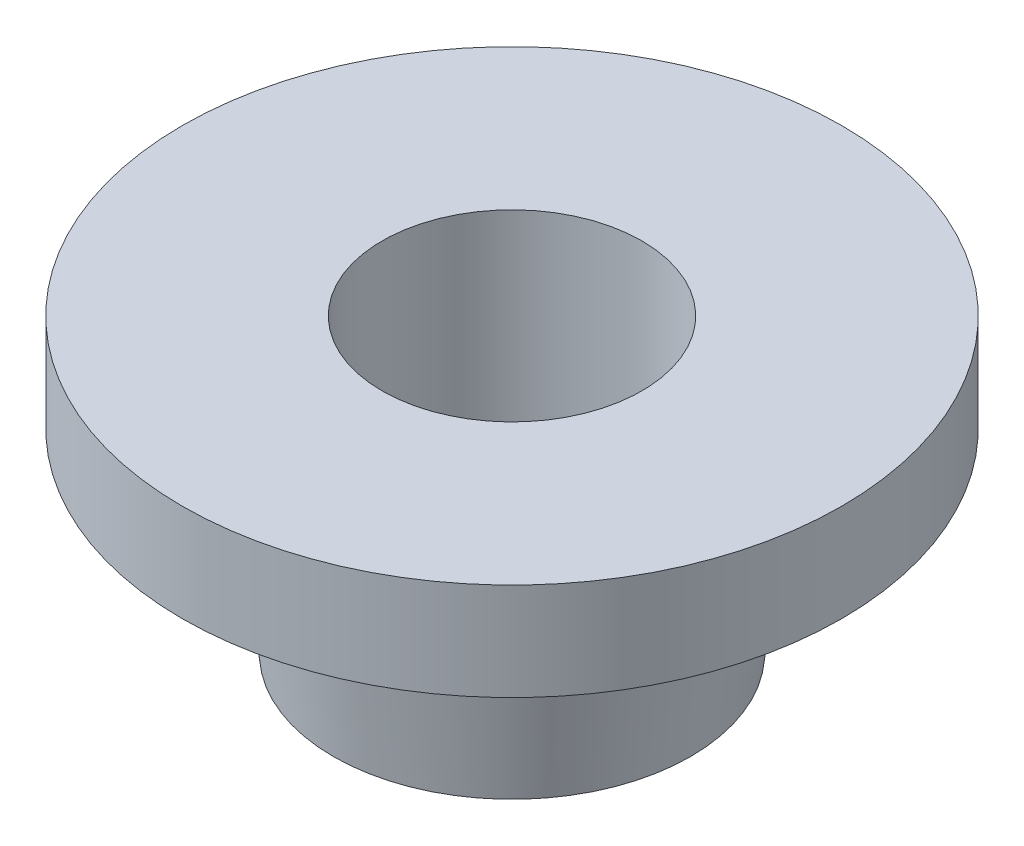
SolidWorks part; units mm, degrees
ref_plane "Front Plane" through (0, 0, 0) normal (0, 0, 1) x (1, 0, 0)
ref_plane "Top Plane" through (0, 0, 0) normal (0, 1, 0) x (1, 0, 0)
ref_plane "Right Plane" through (0, 0, 0) normal (1, 0, 0) x (0, 0, -1)
sketch "Sketch1" plane through (0, 0, 0) normal (0, 0, 1) x (1, 0, 0)
  line L1 (-4, 9) -> (-10.15, 9)
  line L2 (-10.15, 9) -> (-10.15, 6)
  line L3 (-10.15, 6) -> (-6.15, 6)
  line L4 (-6.15, 6) -> (-5.5, 0)
  line L5 (-5.5, 0) -> (-4, 0)
  line L6 (0, 0) -> (0, 9) construction
  line L8 (-4, 9) -> (-4, 0)
  dimension "D1" = 8
  dimension "D2" = 11
  dimension "D3" = 12.3
  dimension "D4" = 6
  dimension "D5" = 3
  dimension "D6" = 4
revolve "Revolve1" add sketch "Sketch1" angle 360 about L6
